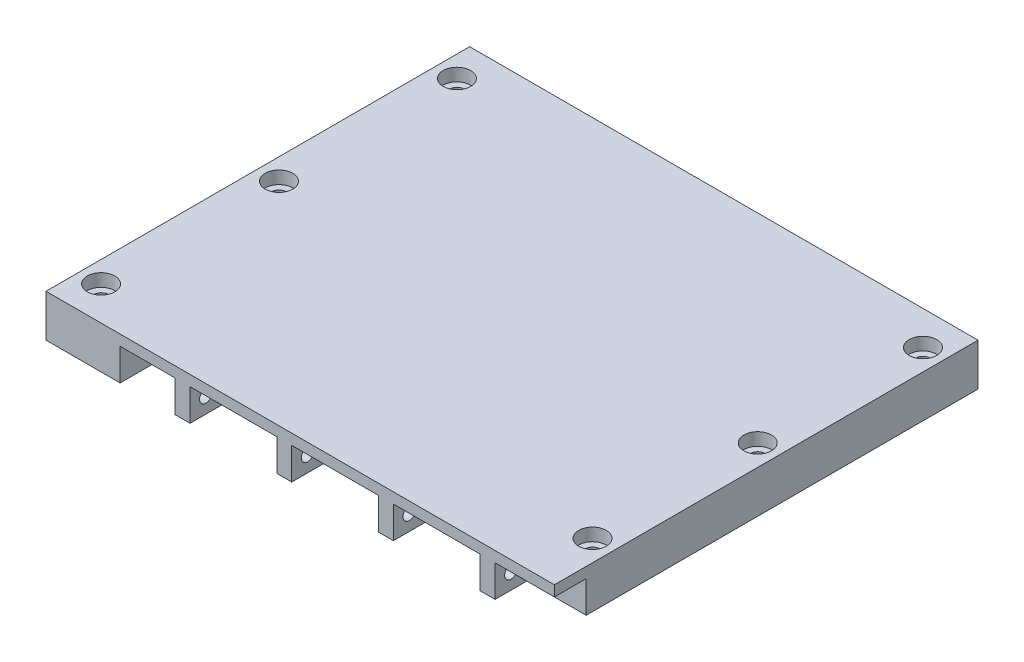
SolidWorks part; units mm, degrees
ref_plane "Front Plane" through (0, 0, 0) normal (0, 0, 1) x (1, 0, 0)
ref_plane "Top Plane" through (0, 0, 0) normal (0, 1, 0) x (1, 0, 0)
ref_plane "Right Plane" through (0, 0, 0) normal (1, 0, 0) x (0, 0, -1)
sketch "Sketch1" plane through (0, 0, 0) normal (0, 1, 0) x (1, 0, 0)
  line L1 (60, -50) -> (-60, -50)
  line L2 (60, -50) -> (60, 50)
  line L3 (60, 50) -> (-60, 50)
  line L4 (-60, -50) -> (-60, 50)
  line L5 (60, -50) -> (-60, 50) construction
  line L6 (60, 50) -> (-60, -50) construction
  point P0 (0, 0)
  dimension "D1" = 120
  dimension "D2" = 100
extrude "Boss-Extrude1" add sketch "Sketch1" along normal blind 10 contours L3 L1 | L3 L4 L1 | L3 L1 L2 region at (0, 0, 0)
sketch "Sketch2" plane through (0, 0, 50) normal (0, 0, 1) x (1, 0, 0)
  line L0 (-60, 0) -> (60, 0) construction
  line L4 (-29.5, -7.5) -> (-42.5, -7.5)
  line L5 (-29.5, -7.5) -> (-29.5, 7.5)
  line L6 (-29.5, 7.5) -> (-42.5, 7.5)
  line L7 (-42.5, -7.5) -> (-42.5, 7.5)
  line L8 (-29.5, -7.5) -> (-42.5, 7.5) construction
  line L9 (-29.5, 7.5) -> (-42.5, -7.5) construction
  line L10 (-5.5, -7.5) -> (-18.5, -7.5)
  line L11 (-5.5, -7.5) -> (-5.5, 7.5)
  line L12 (-5.5, 7.5) -> (-18.5, 7.5)
  line L13 (-18.5, -7.5) -> (-18.5, 7.5)
  line L14 (-5.5, -7.5) -> (-18.5, 7.5) construction
  line L15 (-5.5, 7.5) -> (-18.5, -7.5) construction
  line L16 (18.5, -7.5) -> (5.5, -7.5)
  line L17 (18.5, -7.5) -> (18.5, 7.5)
  line L18 (18.5, 7.5) -> (5.5, 7.5)
  line L19 (5.5, -7.5) -> (5.5, 7.5)
  line L20 (18.5, -7.5) -> (5.5, 7.5) construction
  line L21 (18.5, 7.5) -> (5.5, -7.5) construction
  line L22 (42.5, -7.5) -> (29.5, -7.5)
  line L23 (42.5, -7.5) -> (42.5, 7.5)
  line L24 (42.5, 7.5) -> (29.5, 7.5)
  line L25 (29.5, -7.5) -> (29.5, 7.5)
  line L26 (42.5, -7.5) -> (29.5, 7.5) construction
  line L27 (42.5, 7.5) -> (29.5, -7.5) construction
  line L29 (60, 0) -> (-60, 0) construction
  point P7 (-36, 0)
  point P8 (-12, 0)
  point P9 (12, 0)
  point P10 (36, 0)
  point P11 (-36, 0)
  point P16 (-12, 0)
  point P21 (12, 0)
  point P26 (36, 0)
  point P33 (0, 0)
  dimension "D1" = 120
  dimension "D3" = 13
  dimension "D4" = 15
extrude "Cut-Extrude1" cut sketch "Sketch2" against normal blind 35
sketch "Sketch3" plane through (0, 0, 50) normal (0, 0, 1) x (1, 0, 0)
  line L0 (60, 10) -> (60, 0) construction
  line L1 (-18.5, 0) -> (-26, 0)
  line L2 (-18.5, 0) -> (-18.5, 7.5)
  line L3 (-18.5, 7.5) -> (-26, 7.5)
  line L4 (-26, 0) -> (-26, 7.5)
  line L5 (5.5, 0) -> (-2, 0)
  line L6 (5.5, 0) -> (5.5, 7.5)
  line L7 (5.5, 7.5) -> (-2, 7.5)
  line L8 (-2, 0) -> (-2, 7.5)
  line L9 (29.5, 0) -> (22, 0)
  line L10 (29.5, 0) -> (29.5, 7.5)
  line L11 (29.5, 7.5) -> (22, 7.5)
  line L12 (22, 0) -> (22, 7.5)
  line L13 (46, 0) -> (60, 0)
  line L14 (46, 0) -> (46, 7.5)
  line L15 (46, 7.5) -> (60, 7.5)
  line L16 (60, 0) -> (60, 7.5)
  line L17 (60, 0) -> (42.5, 0) construction
  line L18 (5.5, 7.5) -> (5.5, 0) construction
  line L19 (5.5, 0) -> (-5.5, 0) construction
  line L20 (-5.5, 7.5) -> (-18.5, 7.5) construction
  line L21 (-29.5, 0) -> (-29.5, 7.5) construction
  line L22 (-5.5, 0) -> (-5.5, 7.5) construction
  line L23 (42.5, 0) -> (42.5, 7.5) construction
  line L24 (18.5, 0) -> (18.5, 7.5) construction
  line L25 (-18.5, 0) -> (-5.5, 0) construction
  line L26 (-18.5, 7.5) -> (-18.5, 0) construction
  line L27 (18.5, 7.5) -> (5.5, 7.5) construction
  line L28 (42.5, 7.5) -> (29.5, 7.5) construction
  dimension "D1" = 3.5
  dimension "D2" = 3.5
  dimension "D3" = 3.5
  dimension "D4" = 3.5
extrude "Cut-Extrude2" cut sketch "Sketch3" against normal blind 7.5
sketch "Sketch4" plane through (46, 0, 0) normal (1, 0, 0) x (0, 0, -1)
  line L1 (-42.5, 0) -> (-50, 0) construction
  line L2 (-50, 10) -> (-50, 7.5) construction
  circle A0 centre (-46.25, 3.75) radius 1.5
  dimension "D1" = 3
  dimension "D2" = 3.75
  dimension "D3" = 3.75
extrude "Cut-Extrude3" cut sketch "Sketch4" against normal up to surface (75.5 mm away) up to face at (-29.5, 3.75, 32.5)
hole_wizard "CBORE for M3 SHCS" positions "Sketch7" profile "Sketch8" counterbore size "M3" standard "ANSI Metric"
sketch "Sketch7" plane through (-676.2935, 10, -1323.2827) normal (0, 1, 0) x (1, 0, 0)
  line L3 (621.2935, -1281.2827) -> (621.2935, -1365.2827) construction
  line L5 (731.2935, -1281.2827) -> (731.2935, -1359.2827) construction
  circle A0 centre (731.2935, -1281.2827) radius 2.243
  circle A1 centre (731.2935, -1359.2827) radius 2.2384
  circle A3 centre (621.2935, -1281.2827) radius 2.3325
  circle A4 centre (621.2935, -1365.2827) radius 1.7576
  circle A5 centre (621.2935, -1323.2827) radius 1.8624
  circle A6 centre (731.2935, -1320.2827) radius 2.0271
  point P1 (731.2935, -1281.2827)
  point P8 (731.2935, -1359.2827)
  point P15 (621.2935, -1281.2827)
  point P17 (621.2935, -1365.2827)
  point P19 (621.2935, -1323.2827)
  point P27 (731.2935, -1320.2827)
  point P36 (0, 0)
sketch "Sketch8" plane through (55, 10, -42) normal (1, 0, 0) x (0, 0, 1)
  line L0 (0, 0) -> (0, 24.0215)
  line L1 (0, 24.0215) -> (1.7, 23)
  line L2 (1.7, 23) -> (1.7, 3)
  line L3 (1.7, 3) -> (3.25, 3)
  line L4 (3.25, 3) -> (3.25, 0)
  line L5 (3.25, 0) -> (0, 0)
  line L6 (0, 24.0215) -> (-1.7, 23) construction
  line L7 (0, -6.35) -> (0, 107.95) construction
  dimension "Hole Dia." = 3.4
  dimension "Hole Depth" = 23
  dimension "C'Bore Dia." = 6.5
  dimension "C'Bore Depth" = 3
  dimension "Drill Angle" = 118
